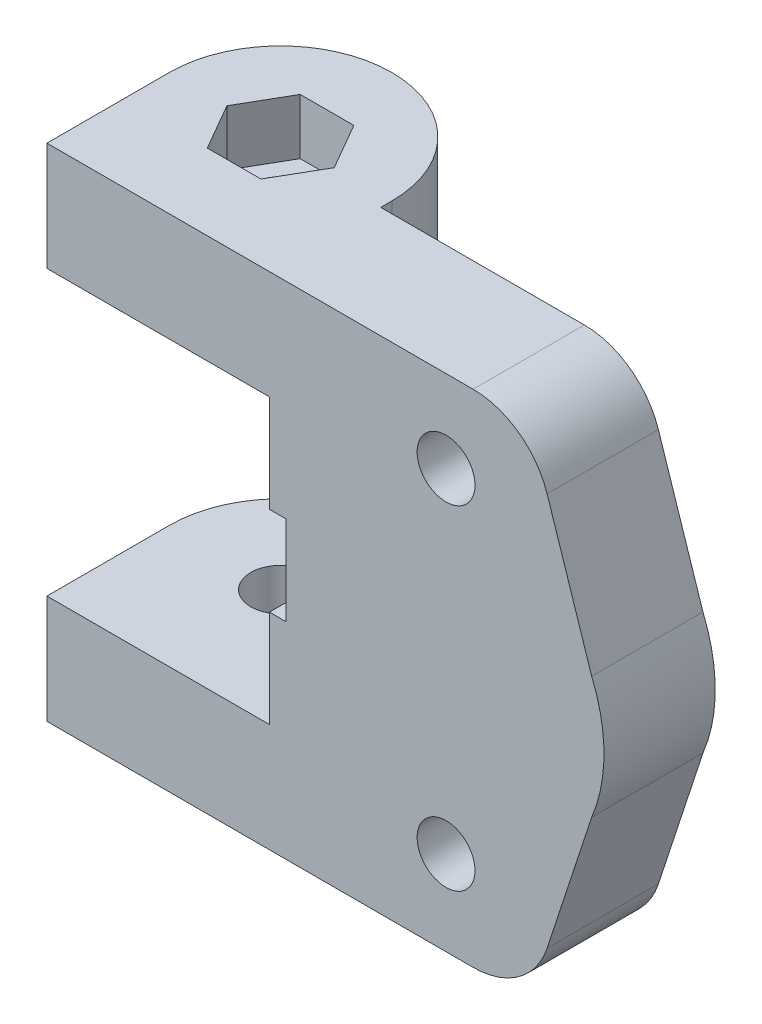
SolidWorks part; units mm, degrees
ref_plane "Front Plane" through (0, 0, 0) normal (0, 0, 1) x (1, 0, 0)
ref_plane "Top Plane" through (0, 0, 0) normal (0, 1, 0) x (1, 0, 0)
ref_plane "Right Plane" through (0, 0, 0) normal (1, 0, 0) x (0, 0, -1)
sketch "Sketch1" plane through (0, 0, 0) normal (0, 0, 1) x (1, 0, 0)
  line L0 (-23.4334, -14.957) -> (-23.4334, -24.707)
  line L1 (12.437, 12.9) -> (12.437, -17.1) construction
  line L2 (-23.4334, 20.293) -> (14.8702, 20.293)
  line L3 (10.0266, -12.925) -> (14.8474, -12.925)
  line L4 (14.8474, 8.725) -> (17.2579, 12.9)
  line L5 (17.2579, 12.9) -> (14.8474, 17.075)
  line L6 (14.8474, 17.075) -> (10.0266, 17.075)
  line L7 (10.0266, 17.075) -> (7.6161, 12.9)
  line L8 (7.6161, 12.9) -> (10.0266, 8.725)
  line L9 (10.0266, 8.725) -> (14.8474, 8.725)
  line L10 (7.6161, -17.1) -> (10.0266, -12.925)
  line L11 (10.0266, -21.275) -> (7.6161, -17.1)
  line L12 (14.8474, -21.275) -> (10.0266, -21.275)
  line L13 (17.2579, -17.1) -> (14.8474, -21.275)
  line L14 (14.8474, -12.925) -> (17.2579, -17.1)
  line L15 (-1.9334, -6.2055) -> (-1.9334, 1.7945)
  line L16 (25.5256, -7.6976) -> (21.5207, -19.8913)
  line L17 (-13.4334, 10.543) -> (-13.4334, -14.957) construction
  line L18 (-1.9334, -6.2055) -> (-3.4334, -6.2055)
  line L19 (-13.4334, -2.207) -> (40.771, -2.207) construction
  line L21 (25.5256, 3.2835) -> (21.5207, 15.4773)
  line L473 (-23.4334, 10.543) -> (-3.4334, 10.543)
  line L475 (-23.4334, -14.957) -> (-3.4334, -14.957)
  line L476 (-23.4334, 20.293) -> (-23.4334, 10.543)
  line L480 (-3.4334, 10.543) -> (-3.4334, 1.7945)
  line L481 (-3.4334, -6.2055) -> (-3.4334, -14.957)
  line L505 (14.8702, -24.707) -> (-23.4334, -24.707)
  line L508 (-3.4334, 1.7945) -> (-1.9334, 1.7945)
  circle A0 centre (12.437, 12.9) radius 2.6
  circle A1 centre (12.437, 12.9) radius 4.175 construction
  circle A2 centre (12.437, -17.1) radius 4.175 construction
  circle A3 centre (12.437, -17.1) radius 2.6
  arc A4 (25.5256, -7.6976) -> (25.5256, 3.2835) centre (12.437, -2.207) ccw
  arc A5 (21.5207, -19.8913) -> (14.8702, -24.707) centre (14.8702, -17.707) cw
  arc A6 (21.5207, 15.4773) -> (14.8702, 20.293) centre (14.8702, 13.293) ccw
  circle A36 centre (12.437, -2.207) radius 9.5
  dimension "D7" = 8.35
  dimension "D5" = 5.2
  dimension "D3" = 35.8704
  dimension "D8" = 8
  dimension "D10" = 19
  dimension "D11" = 7
  dimension "D1" = 45
  dimension "D2" = 25.5
  dimension "D4" = 20
  dimension "D6" = 30
  dimension "D9" = 1.5
extrude "Boss-Extrude1" add sketch "Sketch1" along normal blind 10
sketch "Sketch2" plane through (0, 20.293, 0) normal (0, 1, 0) x (1, 0, 0)
  line L0 (-23.4334, 0) -> (-3.4334, 0)
  line L2 (-13.4334, 10) -> (-23.4334, 10)
  line L3 (-23.4334, 10) -> (-23.4334, 0)
  arc A0 (-3.4334, 0) -> (-13.4334, 10) centre (-13.4334, 0) ccw
extrude "Boss-Extrude4" add sketch "Sketch2" against normal up to vertex
sketch "Sketch18" plane through (0, -24.707, 0) normal (0, -1, 0) x (1, 0, 0)
  line L0 (-23.4334, 0) -> (-3.4334, 0) construction
  line L1 (-13.4334, -10) -> (-23.4334, -10) construction
  line L2 (-23.4334, -10) -> (-23.4334, 0) construction
  line L3 (-23.4334, 0) -> (-3.4334, 0)
  line L4 (-13.4334, -10) -> (-23.4334, -10)
  line L5 (-23.4334, -10) -> (-23.4334, 0)
  arc A0 (-13.4334, -10) -> (-3.4334, 0) centre (-13.4334, 0) ccw construction
  arc A1 (-13.4334, -10) -> (-3.4334, 0) centre (-13.4334, 0) ccw
extrude "Boss-Extrude5" add sketch "Sketch18" against normal blind 9.75
sketch "Sketch19" plane through (0, -24.707, 0) normal (0, -1, 0) x (1, 0, 0)
  circle A0 centre (-13.4334, 0) radius 2.675
  dimension "D1" = 5.35
extrude "Cut-Extrude1" cut sketch "Sketch19" against normal through all
sketch "Sketch20" plane through (0, 0, 0) normal (0, 0, -1) x (-1, 0, 0)
  line L0 (3.4334, -24.707) -> (3.4334, 20.293)
  line L1 (3.4334, 20.293) -> (-35.581, 20.293)
  line L2 (-35.581, 20.293) -> (-33.5581, -24.707)
  line L3 (-33.5581, -24.707) -> (3.4334, -24.707)
extrude "Cut-Extrude2" cut sketch "Sketch20" against normal blind 1
sketch "Sketch21" plane through (0, 0, 10) normal (0, 0, 1) x (1, 0, 0)
  circle A0 centre (12.437, -2.207) radius 9.5415
extrude "Boss-Extrude6" add sketch "Sketch21" against normal blind 8
sketch "Sketch22" plane through (0, 0, 1) normal (0, 0, -1) x (-1, 0, 0)
  line L0 (1.9334, 1.7945) -> (-8.2511, 1.7945)
  line L1 (-8.2511, 1.7945) -> (-8.2511, -6.2055)
  line L2 (-8.2511, -6.2055) -> (1.9334, -6.2055)
  line L3 (1.9334, -6.2055) -> (1.9334, 1.7945)
extrude "Cut-Extrude3" cut sketch "Sketch22" against normal blind 1
sketch "Sketch24" plane through (0, 0, 10) normal (0, 0, 1) x (1, 0, 0)
  line L12 (14.8474, 8.725) -> (17.2579, 12.9) construction
  line L14 (17.2579, 12.9) -> (14.8474, 17.075) construction
  line L17 (14.8474, 17.075) -> (10.0266, 17.075) construction
  line L18 (10.0266, 17.075) -> (7.6161, 12.9) construction
  line L19 (7.6161, 12.9) -> (10.0266, 8.725) construction
  line L20 (10.0266, 8.725) -> (14.8474, 8.725) construction
  line L21 (10.0266, -12.925) -> (14.8474, -12.925) construction
  line L22 (7.6161, -17.1) -> (10.0266, -12.925) construction
  line L23 (10.0266, -21.275) -> (7.6161, -17.1) construction
  line L48 (14.8474, -21.275) -> (10.0266, -21.275) construction
  line L49 (17.2579, -17.1) -> (14.8474, -21.275) construction
  line L50 (14.8474, -12.925) -> (17.2579, -17.1) construction
  line L51 (14.8702, -24.707) -> (-23.4334, -24.707) construction
  line L52 (25.5256, -7.6976) -> (21.5207, -19.8913) construction
  line L53 (25.5256, 3.2835) -> (21.5207, 15.4773) construction
  line L54 (-23.4334, 20.293) -> (14.8702, 20.293) construction
  line L55 (-23.4334, 20.293) -> (-23.4334, 10.543) construction
  line L56 (-23.4334, 10.543) -> (-3.4334, 10.543) construction
  line L57 (-3.4334, 10.543) -> (-3.4334, 1.7945) construction
  line L58 (-3.4334, 1.7945) -> (-1.9334, 1.7945) construction
  line L59 (-1.9334, -6.2055) -> (-1.9334, 1.7945) construction
  line L60 (-1.9334, -6.2055) -> (-3.4334, -6.2055) construction
  line L61 (-3.4334, -6.2055) -> (-3.4334, -14.957) construction
  line L62 (-23.4334, -14.957) -> (-3.4334, -14.957) construction
  line L63 (-23.4334, -14.957) -> (-23.4334, -24.707) construction
  line L64 (14.8474, 8.725) -> (17.2579, 12.9)
  line L65 (17.2579, 12.9) -> (14.8474, 17.075)
  line L66 (14.8474, 17.075) -> (10.0266, 17.075)
  line L67 (10.0266, 17.075) -> (7.6161, 12.9)
  line L68 (7.6161, 12.9) -> (10.0266, 8.725)
  line L69 (10.0266, 8.725) -> (14.8474, 8.725)
  line L70 (10.0266, -12.925) -> (14.8474, -12.925)
  line L71 (7.6161, -17.1) -> (10.0266, -12.925)
  line L72 (10.0266, -21.275) -> (7.6161, -17.1)
  line L73 (14.8474, -21.275) -> (10.0266, -21.275)
  line L74 (17.2579, -17.1) -> (14.8474, -21.275)
  line L75 (14.8474, -12.925) -> (17.2579, -17.1)
  line L76 (14.8702, -24.707) -> (-23.4334, -24.707)
  line L77 (25.5256, -7.6976) -> (21.5207, -19.8913)
  line L78 (25.5256, 3.2835) -> (21.5207, 15.4773)
  line L79 (-23.4334, 20.293) -> (14.8702, 20.293)
  line L80 (-23.4334, 20.293) -> (-23.4334, 10.543)
  line L81 (-23.4334, 10.543) -> (-3.4334, 10.543)
  line L82 (-3.4334, 10.543) -> (-3.4334, 1.7945)
  line L83 (-3.4334, 1.7945) -> (-1.9334, 1.7945)
  line L84 (-1.9334, -6.2055) -> (-1.9334, 1.7945)
  line L85 (-1.9334, -6.2055) -> (-3.4334, -6.2055)
  line L86 (-3.4334, -6.2055) -> (-3.4334, -14.957)
  line L87 (-23.4334, -14.957) -> (-3.4334, -14.957)
  line L88 (-23.4334, -14.957) -> (-23.4334, -24.707)
  circle A3 centre (12.437, -17.1) radius 2.6 construction
  circle A4 centre (12.437, 12.9) radius 2.6 construction
  arc A7 (14.8702, -24.707) -> (21.5207, -19.8913) centre (14.8702, -17.707) ccw construction
  arc A10 (25.5256, -7.6976) -> (25.5256, 3.2835) centre (12.437, -2.207) ccw construction
  arc A11 (21.5207, 15.4773) -> (14.8702, 20.293) centre (14.8702, 13.293) ccw construction
  circle A13 centre (12.437, -17.1) radius 2.6
  circle A14 centre (12.437, 12.9) radius 2.6
  arc A15 (14.8702, -24.707) -> (21.5207, -19.8913) centre (14.8702, -17.707) ccw
  arc A16 (25.5256, -7.6976) -> (25.5256, 3.2835) centre (12.437, -2.207) ccw
  arc A17 (21.5207, 15.4773) -> (14.8702, 20.293) centre (14.8702, 13.293) ccw
extrude "Boss-Extrude8" add sketch "Sketch24" along normal blind 1
sketch "Sketch25" plane through (0, 0, 11) normal (0, 0, 1) x (1, 0, 0)
  line L0 (14.8474, 8.725) -> (17.2579, 12.9) construction
  line L1 (17.2579, 12.9) -> (14.8474, 17.075) construction
  line L2 (14.8474, 17.075) -> (10.0266, 17.075) construction
  line L3 (10.0266, 17.075) -> (7.6161, 12.9) construction
  line L4 (7.6161, 12.9) -> (10.0266, 8.725) construction
  line L5 (10.0266, 8.725) -> (14.8474, 8.725) construction
  line L6 (10.0266, -12.925) -> (14.8474, -12.925) construction
  line L7 (7.6161, -17.1) -> (10.0266, -12.925) construction
  line L8 (10.0266, -21.275) -> (7.6161, -17.1) construction
  line L9 (14.8474, -21.275) -> (10.0266, -21.275) construction
  line L10 (17.2579, -17.1) -> (14.8474, -21.275) construction
  line L11 (14.8474, -12.925) -> (17.2579, -17.1) construction
  line L12 (14.8702, -24.707) -> (-23.4334, -24.707) construction
  line L13 (25.5256, -7.6976) -> (21.5207, -19.8913) construction
  line L14 (25.5256, 3.2835) -> (21.5207, 15.4773) construction
  line L15 (-23.4334, 20.293) -> (14.8702, 20.293) construction
  line L16 (-23.4334, 20.293) -> (-23.4334, 10.543) construction
  line L17 (-23.4334, 10.543) -> (-3.4334, 10.543) construction
  line L18 (-3.4334, 10.543) -> (-3.4334, 1.7945) construction
  line L19 (-3.4334, 1.7945) -> (-1.9334, 1.7945) construction
  line L20 (-1.9334, -6.2055) -> (-1.9334, 1.7945) construction
  line L21 (-1.9334, -6.2055) -> (-3.4334, -6.2055) construction
  line L22 (-3.4334, -6.2055) -> (-3.4334, -14.957) construction
  line L23 (-23.4334, -14.957) -> (-3.4334, -14.957) construction
  line L48 (-23.4334, -14.957) -> (-23.4334, -24.707) construction
  line L49 (14.8474, 8.725) -> (17.2579, 12.9)
  line L50 (17.2579, 12.9) -> (14.8474, 17.075)
  line L51 (14.8474, 17.075) -> (10.0266, 17.075)
  line L52 (10.0266, 17.075) -> (7.6161, 12.9)
  line L53 (7.6161, 12.9) -> (10.0266, 8.725)
  line L54 (10.0266, 8.725) -> (14.8474, 8.725)
  line L55 (10.0266, -12.925) -> (14.8474, -12.925)
  line L56 (7.6161, -17.1) -> (10.0266, -12.925)
  line L57 (10.0266, -21.275) -> (7.6161, -17.1)
  line L58 (14.8474, -21.275) -> (10.0266, -21.275)
  line L59 (17.2579, -17.1) -> (14.8474, -21.275)
  line L60 (14.8474, -12.925) -> (17.2579, -17.1)
  line L61 (14.8702, -24.707) -> (-23.4334, -24.707)
  line L62 (25.5256, -7.6976) -> (21.5207, -19.8913)
  line L63 (25.5256, 3.2835) -> (21.5207, 15.4773)
  line L64 (-23.4334, 20.293) -> (14.8702, 20.293)
  line L65 (-23.4334, 20.293) -> (-23.4334, 10.543)
  line L66 (-23.4334, 10.543) -> (-3.4334, 10.543)
  line L67 (-3.4334, 10.543) -> (-3.4334, 1.7945)
  line L68 (-3.4334, 1.7945) -> (-1.9334, 1.7945)
  line L69 (-1.9334, -6.2055) -> (-1.9334, 1.7945)
  line L70 (-1.9334, -6.2055) -> (-3.4334, -6.2055)
  line L71 (-3.4334, -6.2055) -> (-3.4334, -14.957)
  line L72 (-23.4334, -14.957) -> (-3.4334, -14.957)
  line L73 (-23.4334, -14.957) -> (-23.4334, -24.707)
  circle A0 centre (12.437, -17.1) radius 2.6 construction
  circle A1 centre (12.437, 12.9) radius 2.6 construction
  arc A2 (14.8702, -24.707) -> (21.5207, -19.8913) centre (14.8702, -17.707) ccw construction
  arc A3 (25.5256, -7.6976) -> (25.5256, 3.2835) centre (12.437, -2.207) ccw construction
  arc A4 (21.5207, 15.4773) -> (14.8702, 20.293) centre (14.8702, 13.293) ccw construction
  circle A10 centre (12.437, -2.207) radius 9.5 construction
  circle A11 centre (12.437, -17.1) radius 2.6
  circle A12 centre (12.437, 12.9) radius 2.6
  arc A13 (14.8702, -24.707) -> (21.5207, -19.8913) centre (14.8702, -17.707) ccw
  arc A14 (25.5256, -7.6976) -> (25.5256, 3.2835) centre (12.437, -2.207) ccw
  arc A15 (21.5207, 15.4773) -> (14.8702, 20.293) centre (14.8702, 13.293) ccw
  circle A16 centre (12.437, -2.207) radius 9.5
extrude "Boss-Extrude9" add sketch "Sketch25" against normal blind 5
sketch "Sketch26" plane through (0, -24.707, 0) normal (0, -1, 0) x (1, 0, 0)
  circle A0 centre (-13.4334, 0) radius 4.5
  dimension "D1" = 9
extrude "Cut-Extrude4" cut sketch "Sketch26" against normal blind 5
sketch "Sketch27" plane through (0, 20.293, 0) normal (0, 1, 0) x (1, 0, 0)
  line L0 (-13.4334, 10) -> (-23.4334, 10) construction
  line L1 (-8.6126, 0) -> (-11.023, 4.175)
  line L2 (-11.023, 4.175) -> (-15.8439, 4.175)
  line L3 (-15.8439, 4.175) -> (-18.2543, 0)
  line L4 (-18.2543, 0) -> (-15.8439, -4.175)
  line L5 (-15.8439, -4.175) -> (-11.023, -4.175)
  line L6 (-11.023, -4.175) -> (-8.6126, 0)
  circle A0 centre (-13.4334, 0) radius 4.175 construction
  dimension "D1" = 8.35
extrude "Cut-Extrude5" cut sketch "Sketch27" against normal blind 5
fillet "Fillet1" radius 3 1 edges at (-1.9334, -2.2055, 2)
fillet "Fillet2" radius 10 2 edges at (-23.4334, -19.832, -10) (-23.4334, 15.418, -10)
